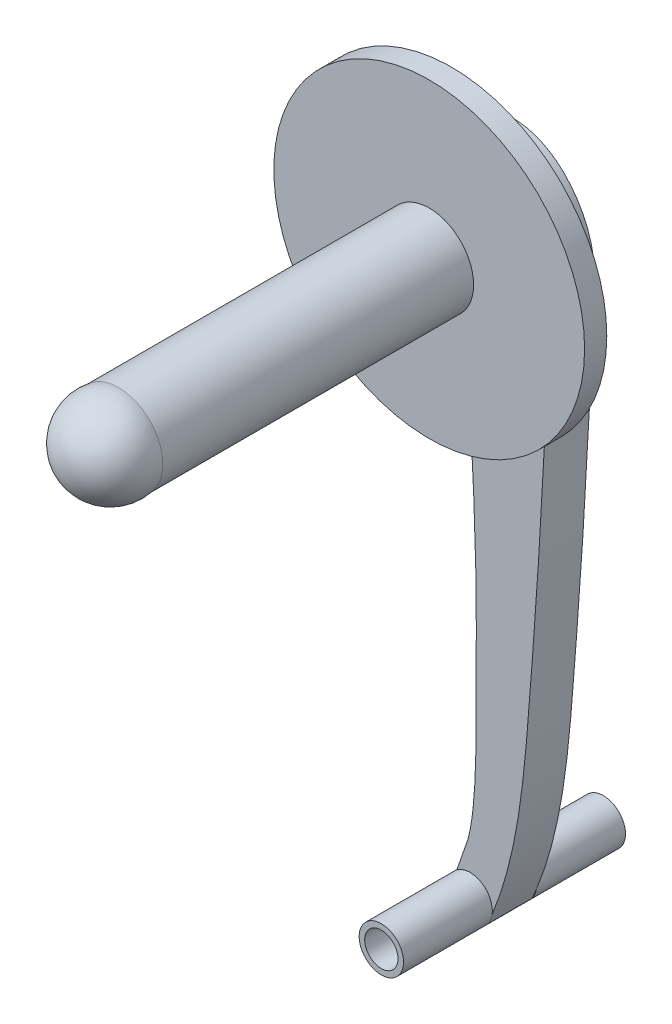
SolidWorks part; units mm, degrees
material "1060 Alloy"
ref_plane "Front Plane" through (0, 0, 0) normal (0, 0, 1) x (1, 0, 0)
ref_plane "Top Plane" through (0, 0, 0) normal (0, 1, 0) x (1, 0, 0)
ref_plane "Right Plane" through (0, 0, 0) normal (1, 0, 0) x (0, 0, -1)
sketch "Sketch1" plane through (0, 0, 0) normal (0, 0, 1) x (1, 0, 0)
  line L1 (-0.3101, 7.1333) -> (0, 8.4889)
  arc A0 (2.5066, -1.9487) -> (-1.9115, 2.5351) centre (0, 0) cw
  arc A1 (0, 93.3172) -> (-22.4234, 80.1517) centre (0, 67.6388) ccw
  spline S0 degree 3 poles (0, 93.3172) (5.0992, 93.2068) (12.414, 85.5621) (10.9118, 68.4915) (10.095, 49.9829) (8.2387, 25.0556) (6.7918, 7.6445) (2.5066, -1.9487) knots 0 0 0 0 0.141746 0.264047 0.48824 0.695067 1 1 1 1
  spline S1 degree 3 poles (-22.4234, 80.1517) (-23.0982, 78.4849) (-21.7102, 73.6578) (-19.9827, 68.7678) (-12.4534, 67.1677) (-8.2443, 69.3092) (0.0454, 67.6805) (0.4045, 52.7492) (0.9638, 37.5962) (0.8468, 32.3426) (0.8582, 19.9212) (0.8237, 12.7445) (0, 8.4889) knots 0 0 0 0 0.058727 0.134626 0.15681 0.26682 0.30417 0.492961 0.537826 0.707954 0.747033 0.907349 0.907349 0.907349 0.907349
  spline S2 degree 2 poles (-1.9115, 2.5351) (-1.0823, 4.8244) (-0.3101, 7.1333) knots 0 0 0 1 1 1
  point P4 (0, 10.5196)
  point P11 (0.0871, 10.6196)
  point P15 (0, 9.665)
  point P19 (0.2382, 10.9722)
  point P20 (0, 8.9074)
  point P21 (0.2466, 10.1793)
  point P23 (-0.1548, 7.9372)
  point P24 (0, 8.4889)
  point P26 (-0.3101, 7.1333)
  dimension "D1" = 3.175
  dimension "D2" = 25.6784
  dimension "D3" = 0.6994
  dimension "D4" = 0.8529
  dimension "D5" = 2.5066
  dimension "D6" = 5.6818
  dimension "D7" = 6.1387
  dimension "D8" = 8.4606
  dimension "D9" = 9.9473
  dimension "D10" = 10.6106
  dimension "D11" = 11.2944
  dimension "D12" = 1.9115
  dimension "D13" = 5.4427
  dimension "D14" = 17.096
  dimension "D15" = 21.8691
  dimension "D16" = 22.4234
  dimension "D17" = 9.492
  dimension "D19" = 25.781
  dimension "D20" = 28.3658
  dimension "D21" = 44.7302
  dimension "D22" = 49.353
  dimension "D23" = 67.6388
  dimension "D24" = 68.1924
  dimension "D25" = 68.7001
  dimension "D26" = 72.1193
  dimension "D27" = 74.3932
  dimension "D29" = 84.5417
  dimension "D30" = 91.3529
extrude "Arm Extrude" add sketch "Sketch1" along normal blind 6.35
sketch "Sketch2" plane through (0, 0, 6.35) normal (0, 0, 1) x (1, 0, 0)
  circle A0 centre (0.495, 82.55) radius 9.525
  point P2 (0, 0)
  point P4 (0, 0)
  point P6 (0, 0)
  dimension "D1" = 19.05
  dimension "D2" = 82.55
extrude "Arm-Handle Spacer Extrude" add sketch "Sketch2" along normal blind 3.175
sketch "Sketch3" plane through (0, 0, 9.525) normal (0, 0, 1) x (1, 0, 0)
  circle A0 centre (0.495, 82.55) radius 22.225
  point P3 (0, 0)
  point P5 (0.495, 82.55)
  dimension "D1" = 44.45
extrude "Handle Base Extrude" add sketch "Sketch3" along normal blind 3.175
sketch "Sketch5" plane through (0, 0, 12.7) normal (0, 0, 1) x (1, 0, 0)
  circle A0 centre (0.495, 82.55) radius 6.35
  circle A2 centre (0.495, 82.55) radius 22.225 construction
  point P2 (0, 0)
  point P3 (0, 0)
  point P4 (0, 0)
  dimension "D1" = 12.7
extrude "Handle Extrude" add sketch "Sketch5" along normal blind 44.45 contours A0
dome "Handle Dome" faces to dome 1 distance 7.62 reverse direction no elliptical dome no face at (6.845, 82.55, 57.15) parameters "D1"=7.62
sketch "Sketch7" plane through (0, 0, 6.35) normal (0, 0, 1) x (1, 0, 0)
  circle A0 centre (0, 0) radius 3.175
  arc A3 (-1.9115, 2.5351) -> (2.5066, -1.9487) centre (0, 0) ccw construction
  point P3 (0, 0)
extrude "Arm Slider Front Extrude" add sketch "Sketch7" along normal blind 12.7
ref_plane "Arm Slider Mirror Plane" through (0, 0, 3.175) normal (0, 0, 1) x (1, 0, 0)
mirror "Arm Slider Back Mirror" about plane through (0, 0, 3.175) normal (0, 0, 1) of "Arm Slider Front Extrude"
sketch "Sketch8" plane through (0, 0, 19.05) normal (0, 0, 1) x (1, 0, 0)
  circle A0 centre (0, 0) radius 2.3812
  circle A1 centre (0, 0) radius 3.175 construction
  dimension "D1" = 4.7625
extrude "Cut-Extrude2" cut sketch "Sketch8" against normal through all
